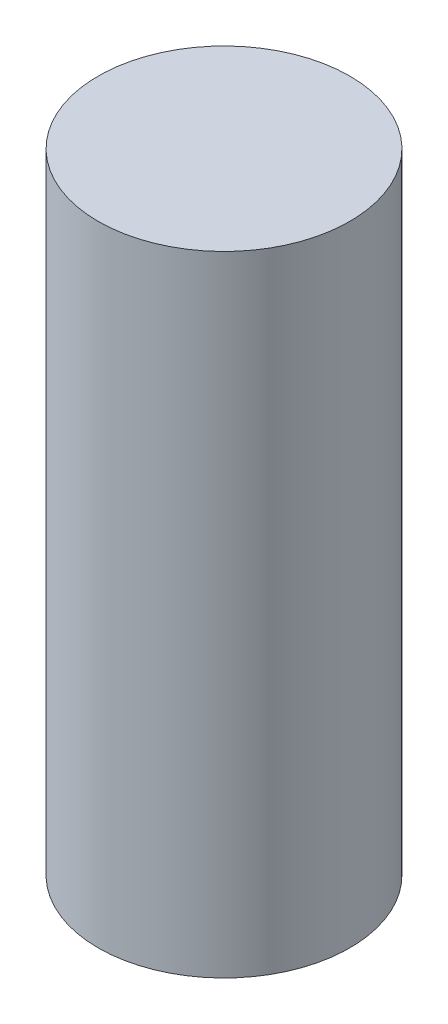
SolidWorks part; units mm, degrees
ref_plane "Front Plane" through (0, 0, 0) normal (0, 0, 1) x (1, 0, 0)
ref_plane "Top Plane" through (0, 0, 0) normal (0, 1, 0) x (1, 0, 0)
ref_plane "Right Plane" through (0, 0, 0) normal (1, 0, 0) x (0, 0, -1)
sketch "Sketch2" plane through (0, 0, 0) normal (0, 1, 0) x (1, 0, 0)
  circle A0 centre (0, 0) radius 30
  dimension "D1" = 60
extrude "Boss-Extrude1" add sketch "Sketch2" along normal blind 150
sketch "Sketch3" plane through (0, 0, 0) normal (1, 0, 0) x (0, 0, -1)
  line L0 (0, 0) -> (0, 50)
  circle A0 centre (0, 50) radius 20
  dimension "D2" = 40
  dimension "D1" = 50
extrude "Cut-Extrude1" cut sketch "Sketch3" against normal blind 100 contours A0 region at (0, 36.2579, -13.7421)
